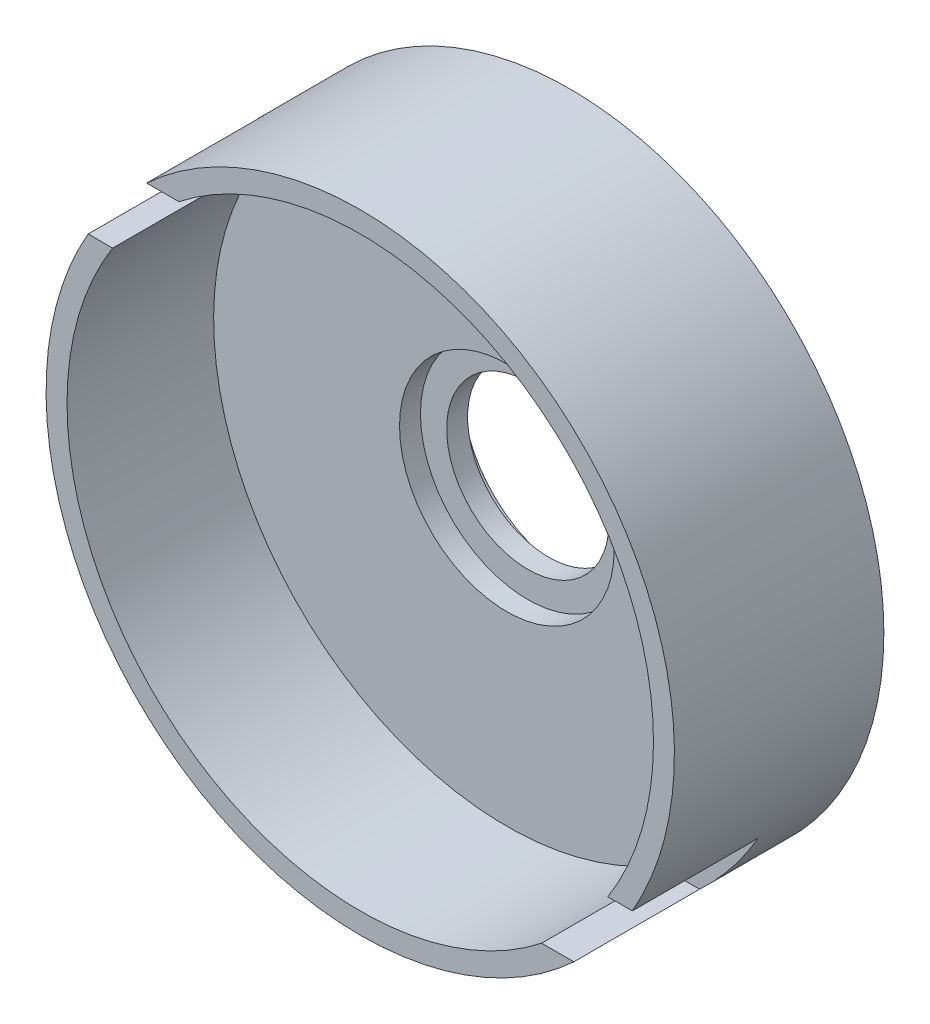
SolidWorks part; units mm, degrees
ref_plane "Спереди" through (0, 0, 0) normal (0, 0, 1) x (1, 0, 0)
ref_plane "Сверху" through (0, 0, 0) normal (0, 1, 0) x (1, 0, 0)
ref_plane "Справа" through (0, 0, 0) normal (1, 0, 0) x (0, 0, -1)
sketch "Эскиз5" plane through (0, 0, 0) normal (0, 0, 1) x (1, 0, 0)
  circle A0 centre (0, 0) radius 30
  dimension "D1" = 60
extrude "Бобышка-Вытянуть1" add sketch "Эскиз5" along normal blind 20
sketch "Эскиз6" plane through (0, 0, 0) normal (0, 0, 1) x (1, 0, 0)
  circle A0 centre (0, 0) radius 28
  dimension "D1" = 56
extrude "Вырез-Вытянуть1" cut sketch "Эскиз6" along normal blind 14 from offset 6
sketch "Эскиз7" plane through (0, 0, 0) normal (0, 0, 1) x (1, 0, 0)
  circle A0 centre (0, 0) radius 7.75
  dimension "D1" = 15.5
extrude "Вырез-Вытянуть2" cut sketch "Эскиз7" along normal blind 15
sketch "Эскиз8" plane through (0, 0, 0) normal (0, 0, 1) x (1, 0, 0)
  circle A0 centre (0, 0) radius 10.25
  dimension "D1" = 20.5
extrude "Вырез-Вытянуть3" cut sketch "Эскиз8" along normal blind 16 from offset 4
sketch "Эскиз10" plane through (0, 0, 0) normal (0, 0, 1) x (1, 0, 0)
  line L1 (-30, 15) -> (-15, 15)
  line L2 (-30, 15) -> (-30, 22)
  line L3 (-30, 22) -> (-15, 22)
  line L4 (-15, 15) -> (-15, 22)
  dimension "D1" = 15
  dimension "D2" = 15
  dimension "D3" = 7
  dimension "D4" = 15
extrude "Вырез-Вытянуть4" cut sketch "Эскиз10" along normal blind 12 from offset 8
sketch "Эскиз13" plane through (0, 0, 0) normal (0, 0, 1) x (1, 0, 0)
  line L1 (15, -15) -> (30, -15)
  line L2 (15, -15) -> (15, -22)
  line L3 (15, -22) -> (30, -22)
  line L4 (30, -15) -> (30, -22)
  dimension "D1" = 15
  dimension "D2" = 15
  dimension "D3" = 15
  dimension "D4" = 7
extrude "Вырез-Вытянуть5" cut sketch "Эскиз13" along normal blind 12 from offset 8
sketch "Эскиз14" plane through (0, 0, 0) normal (0, 0, 1) x (1, 0, 0)
  circle A0 centre (0, 0) radius 10.25
  dimension "D1" = 20.5
extrude "Вырез-Вытянуть6" cut sketch "Эскиз14" along normal blind 2
